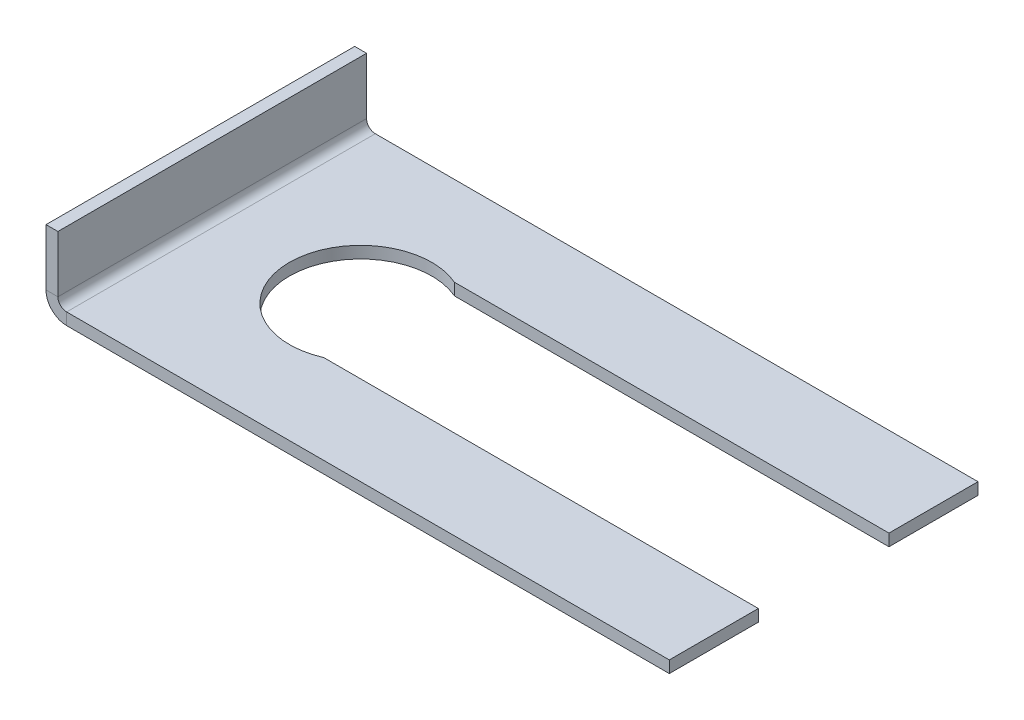
SolidWorks part; units mm, degrees
note: The reader was unsure of these and kept them because the rebuilt part matched: flange length of "Tôle pliée sur arête1".
ref_plane "Plan de face" through (0, 0, 0) normal (0, 0, 1) x (1, 0, 0)
ref_plane "Plan de dessus" through (0, 0, 0) normal (0, 1, 0) x (1, 0, 0)
ref_plane "Plan de droite" through (0, 0, 0) normal (1, 0, 0) x (0, 0, -1)
sketch "Esquisse1" plane through (0, 0, 0) normal (0, 1, 0) x (1, 0, 0)
  line L0 (-55, 0) -> (55, 0) construction
  line L1 (-26.25, -13) -> (26.25, -13)
  line L2 (-26.25, -13) -> (-26.25, 13)
  line L3 (-26.25, 13) -> (26.25, 13)
  line L4 (26.25, -13) -> (26.25, -5.5)
  line L5 (-26.25, -13) -> (26.25, 13) construction
  line L6 (-26.25, 13) -> (26.25, -13) construction
  line L7 (-10.3521, 5.5) -> (26.25, 5.5)
  line L8 (-10.3521, -5.5) -> (26.25, -5.5)
  line L9 (26.25, 5.5) -> (26.25, 13)
  arc A0 (-10.3521, 5.5) -> (-10.3521, -5.5) centre (-12.75, 0) ccw
  point P0 (0, 0)
  dimension "D3" = 12
  dimension "D4" = 13.5
  dimension "D1" = 26
  dimension "D2" = 52.5
  dimension "D5" = 11
base flange "Tôle de base pliée1" sketch "Esquisse1" thickness 1 reverse thickness direction no parameters "D1"=0.7366
edge flange "Tôle pliée sur arête1" sketch "Esquisse12" flange angle 90 flange length 5.5 flange position material inside bend radius 0.7366 thickness 1 relief rectangular parameters "D6"=10
sketch "Esquisse12" plane through (-26.25, 0, 0) normal (-1, 0, 0) x (0, 0, 1)
  line L0 (-13, 0) -> (13, 0) construction
  line L1 (-13, 0) -> (13, 0)
  line L2 (-13, 0) -> (-13, 5.5)
  line L3 (-13, 5.5) -> (13, 5.5)
  line L4 (13, 5.5) -> (13, 0)
bend "Pli d'arête1" bend radius 0.7366 bend angle 90 parameters "D5"=1
sketch "Esquisse13" plane through (0, 0, 0) normal (0, 0, 1) x (1, 0, 0)
  line L0 (-18.75, 0) -> (-18.75, -1) construction
sketch "Lignes de pliage3" [suppressed] plane through (0, 0, 0) normal (0, 1, 0) x (1, 0, 0)
sketch "Cube de visualisation3" [suppressed] plane through (0, 0, 0) normal (0, 1, 0) x (1, 0, 0)
sheet metal parameters "Tôlerie3" thickness 1 parameters "D1"=0.7366
flat pattern "Etat déplié3" [suppressed]
sketch "Lignes de pliage4" plane through (0, 0, 0) normal (0, 1, 0) x (1, 0, 0)
sketch3d "Cube de visualisation4" [suppressed]
  line L0 (-39, -13, 0) -> (13.5, -13, 0) construction
  line L1 (-39, 13, 0) -> (13.5, 13, 0) construction
  line L2 (-39, -13, 0) -> (-39, 13, 0) construction
  line L3 (13.5, -13, 0) -> (13.5, 13, 0) construction
sheet metal parameters "Tôlerie4" thickness 1 parameters "D1"=0.7366
flat pattern "Etat déplié3"
sketch "Lignes de pliage4" plane through (0, 0, 0) normal (0, 1, 0) x (1, 0, 0)
  line L0 (-25.4846, 13) -> (-25.4846, -13) construction
  line L1 (-25.4846, 13) -> (-25.4846, -13) construction
sketch3d "Cube de visualisation4" [suppressed]
  line L0 (39, -13, 0) -> (-18.4692, -13, 0) construction
  line L1 (39, 13, 0) -> (-18.4692, 13, 0) construction
  line L2 (39, -13, 0) -> (39, 13, 0) construction
  line L3 (-18.4692, -13, 0) -> (-18.4692, 13, 0) construction
bend of the flat pattern "Dépliage-<Pli d'arête1>1"
